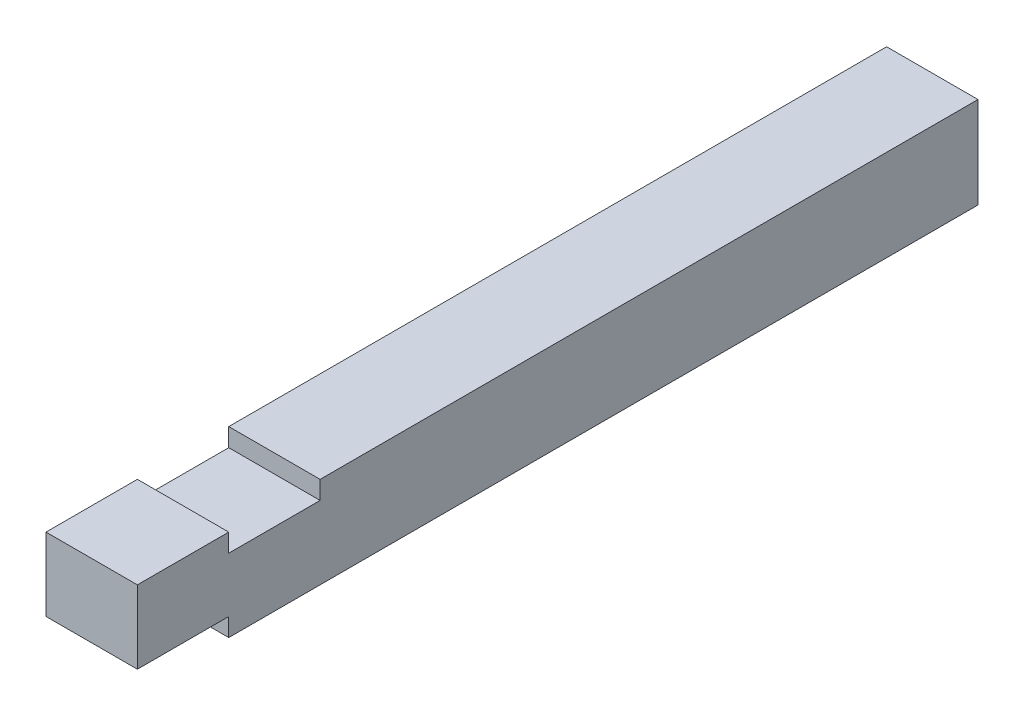
SolidWorks part; units mm, degrees
ref_plane "Plan de face" through (0, 0, 0) normal (0, 0, 1) x (1, 0, 0)
ref_plane "Plan de dessus" through (0, 0, 0) normal (0, 1, 0) x (1, 0, 0)
ref_plane "Plan de droite" through (0, 0, 0) normal (1, 0, 0) x (0, 0, -1)
sketch "Esquisse1" plane through (0, 0, 0) normal (0, 0, 1) x (1, 0, 0)
  line L1 (0, 0) -> (10, 0)
  line L2 (0, 0) -> (0, 10)
  line L3 (0, 10) -> (10, 10)
  line L4 (10, 0) -> (10, 10)
  dimension "D1" = 10
  dimension "D2" = 10
extrude "Boss.-Extru.1" add sketch "Esquisse1" along normal blind 92
sketch "Esquisse2" plane through (0, 0, 0) normal (0, -1, 0) x (1, 0, 0)
  line L0 (0, 92) -> (0, 0) construction
  line L1 (10, 92) -> (0, 92)
  line L2 (10, 92) -> (10, 82)
  line L3 (10, 82) -> (0, 82)
  line L4 (0, 92) -> (0, 82)
  dimension "D1" = 10
extrude "Enlèv. mat.-Extru.1" cut sketch "Esquisse2" against normal blind 2
sketch "Esquisse3" plane through (0, 10, 0) normal (0, 1, 0) x (1, 0, 0)
  line L0 (10, -92) -> (10, 0) construction
  line L1 (10, -82) -> (0, -82)
  line L2 (10, -82) -> (10, -72)
  line L3 (10, -72) -> (0, -72)
  line L4 (0, -82) -> (0, -72)
  line L5 (0, -92) -> (0, 0) construction
  line L6 (10, -92) -> (0, -92) construction
  dimension "D1" = 10
  dimension "D2" = 10
extrude "Enlèv. mat.-Extru.2" cut sketch "Esquisse3" against normal blind 2
